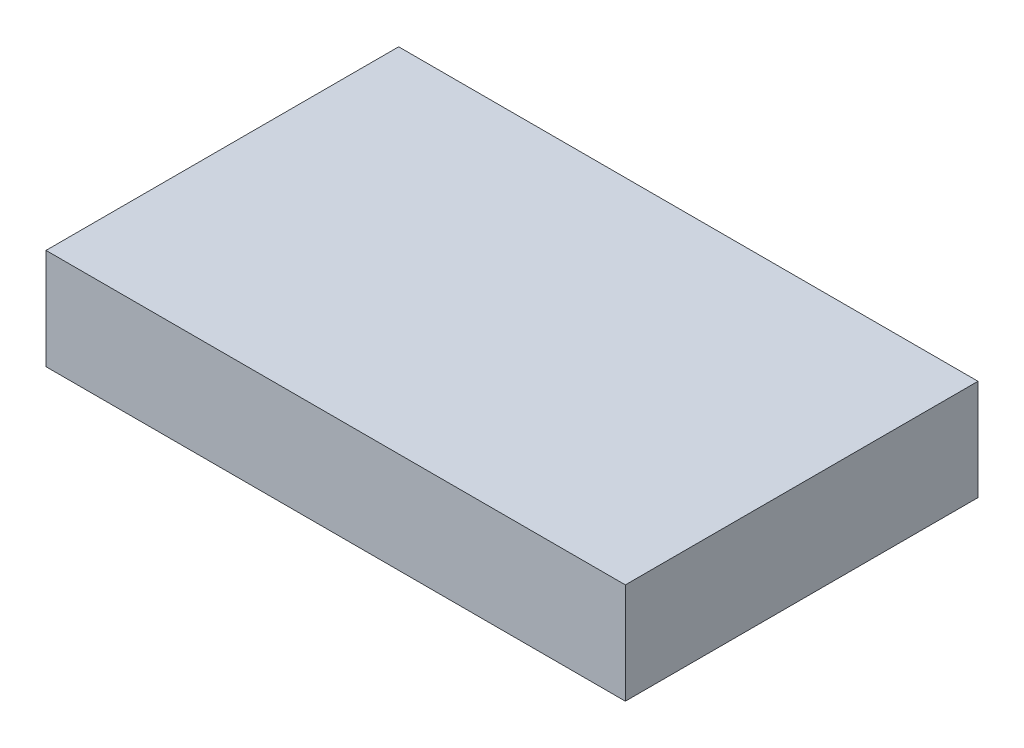
SolidWorks part; units mm, degrees
ref_plane "Front Plane" through (0, 0, 0) normal (0, 0, 1) x (1, 0, 0)
ref_plane "Top Plane" through (0, 0, 0) normal (0, 1, 0) x (1, 0, 0)
ref_plane "Right Plane" through (0, 0, 0) normal (1, 0, 0) x (0, 0, -1)
sketch "Sketch1" plane through (0, 0, 0) normal (0, 1, 0) x (1, 0, 0)
  line L1 (-57.5, -35) -> (57.5, -35)
  line L2 (-57.5, -35) -> (-57.5, 35)
  line L3 (-57.5, 35) -> (57.5, 35)
  line L4 (57.5, -35) -> (57.5, 35)
  line L5 (0, 35) -> (0, -35) construction
  line L6 (-57.5, 0) -> (57.5, 0) construction
  point P0 (0, 0)
  dimension "D1" = 115
  dimension "D2" = 70
extrude "Boss-Extrude1" add sketch "Sketch1" along normal blind 20
